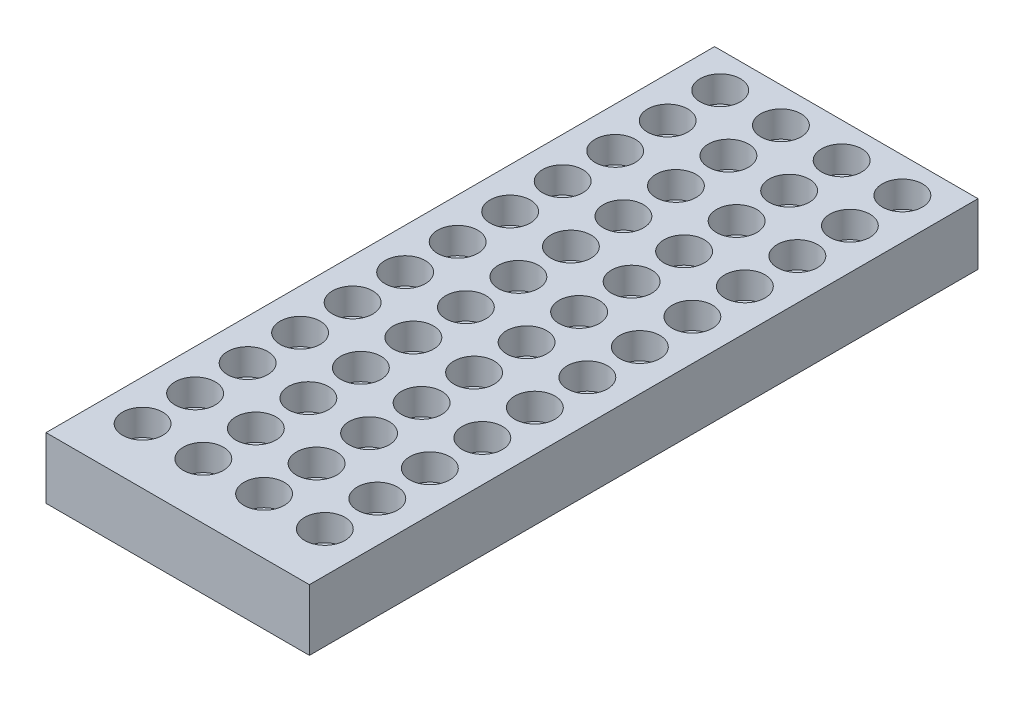
SolidWorks part; units mm, degrees
ref_plane "Front Plane" through (0, 0, 0) normal (0, 0, 1) x (1, 0, 0)
ref_plane "Top Plane" through (0, 0, 0) normal (0, 1, 0) x (1, 0, 0)
ref_plane "Right Plane" through (0, 0, 0) normal (1, 0, 0) x (0, 0, -1)
sketch "Sketch1" plane through (0, 0, 0) normal (0, 1, 0) x (1, 0, 0)
  line L0 (-26.025, 70.5) -> (-37.625, 70.5) construction
  line L1 (37.625, -95.5) -> (-37.625, -95.5)
  line L2 (37.625, -95.5) -> (37.625, 95.5)
  line L3 (37.625, 95.5) -> (-37.625, 95.5)
  line L4 (-37.625, -95.5) -> (-37.625, 95.5)
  line L5 (37.625, -95.5) -> (-37.625, 95.5) construction
  line L6 (37.625, 95.5) -> (-37.625, -95.5) construction
  line L7 (-26.025, 85.5) -> (-37.625, 85.5) construction
  line L8 (-26.025, 85.5) -> (-26.025, 95.5) construction
  line L9 (26.025, 85.5) -> (37.625, 85.5) construction
  line L10 (-14.425, 85.5) -> (-26.025, 85.5) construction
  circle A0 centre (-26.025, 85.5) radius 5.75
  circle A1 centre (-8.675, 85.5) radius 5.75
  circle A2 centre (8.675, 85.5) radius 5.75
  circle A3 centre (26.025, 85.5) radius 5.75
  circle A6 centre (-26.025, 70.5) radius 5.75
  circle A7 centre (-8.675, 70.5) radius 5.75
  circle A8 centre (8.675, 70.5) radius 5.75
  circle A9 centre (26.025, 70.5) radius 5.75
  circle A12 centre (-26.025, 55.5) radius 5.75
  circle A13 centre (-8.675, 55.5) radius 5.75
  circle A14 centre (8.675, 55.5) radius 5.75
  circle A15 centre (26.025, 55.5) radius 5.75
  circle A18 centre (-26.025, 40.5) radius 5.75
  circle A19 centre (-8.675, 40.5) radius 5.75
  circle A20 centre (8.675, 40.5) radius 5.75
  circle A21 centre (26.025, 40.5) radius 5.75
  circle A24 centre (-26.025, 25.5) radius 5.75
  circle A25 centre (-8.675, 25.5) radius 5.75
  circle A26 centre (8.675, 25.5) radius 5.75
  circle A27 centre (26.025, 25.5) radius 5.75
  circle A30 centre (-26.025, 10.5) radius 5.75
  circle A31 centre (-8.675, 10.5) radius 5.75
  circle A32 centre (8.675, 10.5) radius 5.75
  circle A33 centre (26.025, 10.5) radius 5.75
  circle A36 centre (-26.025, -4.5) radius 5.75
  circle A37 centre (-8.675, -4.5) radius 5.75
  circle A38 centre (8.675, -4.5) radius 5.75
  circle A39 centre (26.025, -4.5) radius 5.75
  circle A42 centre (-26.025, -19.5) radius 5.75
  circle A43 centre (-8.675, -19.5) radius 5.75
  circle A44 centre (8.675, -19.5) radius 5.75
  circle A45 centre (26.025, -19.5) radius 5.75
  circle A48 centre (-26.025, -34.5) radius 5.75
  circle A49 centre (-8.675, -34.5) radius 5.75
  circle A50 centre (8.675, -34.5) radius 5.75
  circle A51 centre (26.025, -34.5) radius 5.75
  circle A54 centre (-26.025, -49.5) radius 5.75
  circle A55 centre (-8.675, -49.5) radius 5.75
  circle A56 centre (8.675, -49.5) radius 5.75
  circle A57 centre (26.025, -49.5) radius 5.75
  circle A58 centre (-26.025, -64.5) radius 5.75
  circle A59 centre (-8.675, -64.5) radius 5.75
  circle A60 centre (8.675, -64.5) radius 5.75
  circle A61 centre (26.025, -64.5) radius 5.75
  circle A62 centre (-26.025, -79.5) radius 5.75
  circle A63 centre (-8.675, -79.5) radius 5.75
  circle A64 centre (8.675, -79.5) radius 5.75
  circle A65 centre (26.025, -79.5) radius 5.75
  point P0 (0, 0)
  dimension "D1" = 11.5
  dimension "D3" = 15
  dimension "D5" = 10
  dimension "D7" = 191
  dimension "D9" = 75.25
  dimension "D2" = 4
  dimension "D6" = 12
extrude "Boss-Extrude1" add sketch "Sketch1" along normal blind 7.5
sketch "Sketch2" plane through (0, 0, 0) normal (0, -1, 0) x (1, 0, 0)
  line L1 (37.625, -95.5) -> (-37.625, -95.5)
  line L2 (37.625, -95.5) -> (37.625, 95.5)
  line L3 (37.625, 95.5) -> (-37.625, 95.5)
  line L4 (-37.625, -95.5) -> (-37.625, 95.5)
  line L5 (37.625, -95.5) -> (-37.625, 95.5) construction
  line L6 (37.625, 95.5) -> (-37.625, -95.5) construction
  point P0 (0, 0)
sketch "Sketch3" plane through (0, 0, 0) normal (0, -1, 0) x (1, 0, 0)
  line L0 (37.625, -95.5) -> (-37.625, -95.5) construction
  line L1 (37.625, 95.5) -> (37.625, -95.5) construction
  line L2 (-37.625, -95.5) -> (-37.625, 95.5) construction
  line L3 (-37.625, 95.5) -> (37.625, 95.5) construction
  line L4 (37.625, -95.5) -> (-37.625, -95.5)
  line L5 (37.625, 95.5) -> (37.625, -95.5)
  line L6 (-37.625, -95.5) -> (-37.625, 95.5)
  line L7 (-37.625, 95.5) -> (37.625, 95.5)
extrude "Boss-Extrude2" add sketch "Sketch3" along normal blind 10
